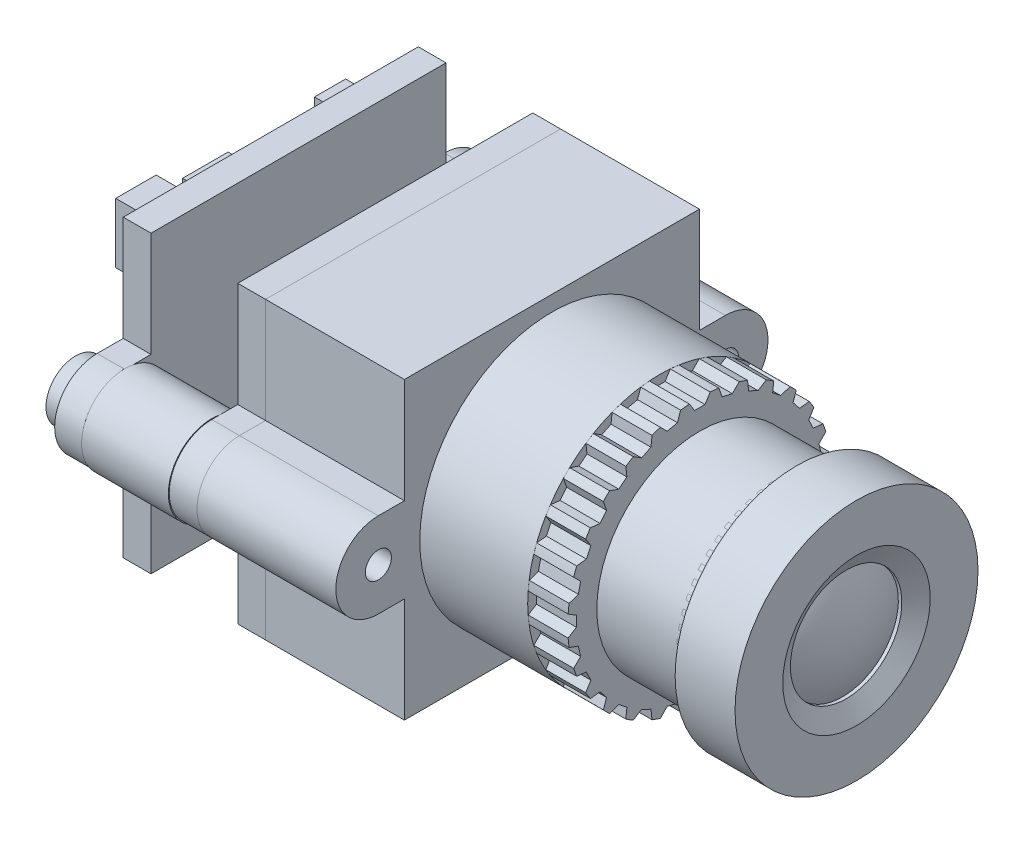
SolidWorks part; units mm, degrees
ref_plane "Front Plane" through (0, 0, 0) normal (0, 0, 1) x (1, 0, 0)
ref_plane "Top Plane" through (0, 0, 0) normal (0, 1, 0) x (1, 0, 0)
ref_plane "Right Plane" through (0, 0, 0) normal (1, 0, 0) x (0, 0, -1)
ref_axis "Axis1" through (-11.8965, 0, 0) along (1, 0, 0)
sketch "Sketch1" plane through (0, 0, 0) normal (1, 0, 0) x (0, 0, -1)
  circle A0 centre (0, 0) radius 7
  dimension "D1" = 14
extrude "Boss-Extrude1" add sketch "Sketch1" against normal blind 3.45
sketch "Sketch2" plane through (-3.45, 0, 0) normal (-1, 0, 0) x (0, 0, 1)
  circle A0 centre (0, 0) radius 5.935
  dimension "D1" = 11.87
extrude "Boss-Extrude2" add sketch "Sketch2" along normal blind 5.58
sketch "Sketch3" plane through (-9.03, 0, 0) normal (-1, 0, 0) x (0, 0, 1)
  circle A0 centre (0, 0) radius 7.61
  dimension "D1" = 15.22
extrude "Boss-Extrude3" add sketch "Sketch3" along normal blind 2.3
sketch "Sketch4" plane through (0, 0, 0) normal (0, 0, 1) x (1, 0, 0)
  line L0 (-3.45, 0) -> (0, 0) construction
  line L1 (-3.45, 5.935) -> (-3.45, -5.935) construction
  line L2 (0, -7) -> (0, 7) construction
  line L3 (0, 7) -> (-3.45, 7) construction
  line L4 (-0.6, 4.25) -> (0, 4.25)
  line L5 (-0.6, 4.25) -> (-0.6, -4.25)
  line L6 (-0.6, -4.25) -> (0, -4.25)
  line L7 (0, 4.25) -> (0, -4.25)
  line L8 (-0.6, 4.25) -> (0, -4.25) construction
  line L9 (-0.6, -4.25) -> (0, 4.25) construction
  line L10 (0, 4.25) -> (-0.6, 3.2108)
  line L11 (-0.8, 0) -> (-0.6, 3.2108) construction
  line L12 (-0.8, -3.2108) -> (-0.6, -3.2108)
  line L13 (-0.8, -3.2108) -> (-0.8, 3.2108)
  line L14 (-0.8, 3.2108) -> (-0.6, 3.2108)
  line L15 (-0.6, -3.2108) -> (-0.6, 3.2108)
  line L16 (-0.8, -3.2108) -> (-0.6, 3.2108) construction
  line L17 (-0.8, 3.2108) -> (-0.6, -3.2108) construction
  line L18 (-0.7, 1.6054) -> (0, 1.6054) construction
  line L19 (-0.8, 0) -> (0, 0)
  line L21 (0, 0) -> (0.6, 0)
  line L22 (0, 0) -> (0, 4.25)
  line L23 (0, 4.25) -> (0.6, 4.25)
  line L24 (0.6, 0) -> (0.6, 4.25)
  spline S0 degree 2 poles (0, 0) (0, 1.7034) (-0.8, 3.2108) knots 0 0 0 1 1 1
  point P6 (-0.3, 0)
  point P15 (-0.7, 0)
  dimension "D1" = 0.6
  dimension "D2" = 2.75
  dimension "D3" = 60
  dimension "D4" = 0.2
  dimension "D5" = 0.6
revolve "Cut-Revolve7" cut sketch "Sketch4" angle 360 about axis through (-11.8965, 0, 0) along (1, 0, 0) region at (0.3, 2.125, 0) region at (-0.2115, 2.72, 0) region at (-0.6658, 3.0768, 0)
sketch "Sketch5" plane through (-9.03, 0, 0) normal (1, 0, 0) x (0, 0, -1)
  line L0 (0, 7.61) -> (0, -7.61) construction
  line L1 (0.6, 7.5863) -> (0.3, 7.11)
  line L2 (0.3, 7.11) -> (-0.3, 7.11)
  line L3 (-0.6, 7.5863) -> (-0.3, 7.11)
  line L4 (2.2731, 7.2626) -> (1.8746, 6.865)
  line L5 (1.8746, 6.865) -> (1.2896, 6.9985)
  line L6 (1.1032, 7.5296) -> (1.2896, 6.9985)
  line L7 (3.8322, 6.5747) -> (3.3552, 6.2757)
  line L8 (3.3552, 6.2757) -> (2.8146, 6.5361)
  line L9 (2.751, 7.0954) -> (2.8146, 6.5361)
  line L10 (5.1991, 5.5571) -> (4.6676, 5.3718)
  line L11 (4.6676, 5.3718) -> (4.1985, 5.7459)
  line L12 (4.2609, 6.3053) -> (4.1985, 5.7459)
  line L13 (6.3053, 4.2609) -> (5.7459, 4.1985)
  line L14 (5.7459, 4.1985) -> (5.3718, 4.6676)
  line L15 (5.5571, 5.1991) -> (5.3718, 4.6676)
  line L16 (7.0954, 2.751) -> (6.5361, 2.8146)
  line L17 (6.5361, 2.8146) -> (6.2757, 3.3552)
  line L18 (6.5747, 3.8322) -> (6.2757, 3.3552)
  line L19 (7.5296, 1.1032) -> (6.9985, 1.2896)
  line L20 (6.9985, 1.2896) -> (6.865, 1.8746)
  line L21 (7.2626, 2.2731) -> (6.865, 1.8746)
  line L22 (7.5863, -0.6) -> (7.11, -0.3)
  line L23 (7.11, -0.3) -> (7.11, 0.3)
  line L24 (7.5863, 0.6) -> (7.11, 0.3)
  line L25 (7.2626, -2.2731) -> (6.865, -1.8746)
  line L26 (6.865, -1.8746) -> (6.9985, -1.2896)
  line L27 (7.5296, -1.1032) -> (6.9985, -1.2896)
  line L28 (6.5747, -3.8322) -> (6.2757, -3.3552)
  line L29 (6.2757, -3.3552) -> (6.5361, -2.8146)
  line L30 (7.0954, -2.751) -> (6.5361, -2.8146)
  line L31 (5.5571, -5.1991) -> (5.3718, -4.6676)
  line L32 (5.3718, -4.6676) -> (5.7459, -4.1985)
  line L33 (6.3053, -4.2609) -> (5.7459, -4.1985)
  line L34 (4.2609, -6.3053) -> (4.1985, -5.7459)
  line L35 (4.1985, -5.7459) -> (4.6676, -5.3718)
  line L36 (5.1991, -5.5571) -> (4.6676, -5.3718)
  line L37 (2.751, -7.0954) -> (2.8146, -6.5361)
  line L38 (2.8146, -6.5361) -> (3.3552, -6.2757)
  line L39 (3.8322, -6.5747) -> (3.3552, -6.2757)
  line L40 (1.1032, -7.5296) -> (1.2896, -6.9985)
  line L41 (1.2896, -6.9985) -> (1.8746, -6.865)
  line L42 (2.2731, -7.2626) -> (1.8746, -6.865)
  line L43 (-0.6, -7.5863) -> (-0.3, -7.11)
  line L44 (-0.3, -7.11) -> (0.3, -7.11)
  line L45 (0.6, -7.5863) -> (0.3, -7.11)
  line L46 (-2.2731, -7.2626) -> (-1.8746, -6.865)
  line L47 (-1.8746, -6.865) -> (-1.2896, -6.9985)
  line L48 (-1.1032, -7.5296) -> (-1.2896, -6.9985)
  line L49 (-3.8322, -6.5747) -> (-3.3552, -6.2757)
  line L50 (-3.3552, -6.2757) -> (-2.8146, -6.5361)
  line L51 (-2.751, -7.0954) -> (-2.8146, -6.5361)
  line L52 (-5.1991, -5.5571) -> (-4.6676, -5.3718)
  line L53 (-4.6676, -5.3718) -> (-4.1985, -5.7459)
  line L54 (-4.2609, -6.3053) -> (-4.1985, -5.7459)
  line L55 (-6.3053, -4.2609) -> (-5.7459, -4.1985)
  line L56 (-5.7459, -4.1985) -> (-5.3718, -4.6676)
  line L57 (-5.5571, -5.1991) -> (-5.3718, -4.6676)
  line L58 (-7.0954, -2.751) -> (-6.5361, -2.8146)
  line L59 (-6.5361, -2.8146) -> (-6.2757, -3.3552)
  line L60 (-6.5747, -3.8322) -> (-6.2757, -3.3552)
  line L61 (-7.5296, -1.1032) -> (-6.9985, -1.2896)
  line L62 (-6.9985, -1.2896) -> (-6.865, -1.8746)
  line L63 (-7.2626, -2.2731) -> (-6.865, -1.8746)
  line L64 (-7.5863, 0.6) -> (-7.11, 0.3)
  line L65 (-7.11, 0.3) -> (-7.11, -0.3)
  line L66 (-7.5863, -0.6) -> (-7.11, -0.3)
  line L67 (-7.2626, 2.2731) -> (-6.865, 1.8746)
  line L68 (-6.865, 1.8746) -> (-6.9985, 1.2896)
  line L69 (-7.5296, 1.1032) -> (-6.9985, 1.2896)
  line L70 (-6.5747, 3.8322) -> (-6.2757, 3.3552)
  line L71 (-6.2757, 3.3552) -> (-6.5361, 2.8146)
  line L72 (-7.0954, 2.751) -> (-6.5361, 2.8146)
  line L73 (-5.5571, 5.1991) -> (-5.3718, 4.6676)
  line L74 (-5.3718, 4.6676) -> (-5.7459, 4.1985)
  line L75 (-6.3053, 4.2609) -> (-5.7459, 4.1985)
  line L76 (-4.2609, 6.3053) -> (-4.1985, 5.7459)
  line L77 (-4.1985, 5.7459) -> (-4.6676, 5.3718)
  line L78 (-5.1991, 5.5571) -> (-4.6676, 5.3718)
  line L79 (-2.751, 7.0954) -> (-2.8146, 6.5361)
  line L80 (-2.8146, 6.5361) -> (-3.3552, 6.2757)
  line L81 (-3.8322, 6.5747) -> (-3.3552, 6.2757)
  line L82 (-1.1032, 7.5296) -> (-1.2896, 6.9985)
  line L83 (-1.2896, 6.9985) -> (-1.8746, 6.865)
  line L84 (-2.2731, 7.2626) -> (-1.8746, 6.865)
  circle A0 centre (0, 0) radius 7.61 construction
  circle A1 centre (0, 0) radius 7.61 construction
  circle A2 centre (0, 0) radius 7.61
  point P12 (0, 7.11)
  point P13 (0, 0)
  point P123 (0, 0)
  circle M6 centre (0, 0) radius 7.61
  dimension "D1" = 0.6
  dimension "D2" = 1.2
  dimension "D3" = 0.5
  dimension "D5" = 0.5063
  dimension "D4" = 28
extrude "Cut-Extrude1" cut sketch "Sketch5" against normal up to next (2.3 mm away) contours L9 L8 L7 M6 | L6 L5 L4 M6 | L0 L2 L1 M6 | L84 L83 L82 M6 | L0 A2 L3 L2 | L81 L80 L79 M6 | L78 L77 L76 M6 | L75 L74 L73 M6 | L72 L71 L70 M6 | L69 L68 L67 M6 | L66 L65 L64 M6 | L63 L62 L61 M6 | L60 L59 L58 M6 | L57 L56 L55 M6 | L51 L50 L49 M6 | L54 L53 L52 M6 | L48 L47 L46 M6 | L0 L44 L43 M6 | L44 L0 A2 L45 | L42 L41 L40 M6 | L39 L38 L37 M6 | L36 L35 L34 M6 | L33 L32 L31 M6 | L30 L29 L28 M6 | L27 L26 L25 M6 | L24 L23 L22 M6 | L21 L20 L19 M6 | L18 L17 L16 M6 | L15 L14 L13 M6 | L12 L11 L10 M6 region at (-9.03, 7.384, -0.233) region at (-9.03, 7.384, 0.233) region at (-9.03, -7.384, -0.233) region at (-9.03, -7.384, 0.233) region at (-9.03, 7.1989, -1.6431) region at (-9.03, 7.1989, 1.6431) region at (-9.03, 6.6527, -3.2038) region at (-9.03, 6.6527, 3.2038) region at (-9.03, -7.1989, 1.6431) region at (-9.03, -7.1989, -1.6431) region at (-9.03, 5.773, -4.6038) region at (-9.03, 5.773, 4.6038) region at (-9.03, -6.6527, 3.2038) region at (-9.03, -6.6527, -3.2038) region at (-9.03, 4.6038, -5.773) region at (-9.03, 4.6038, 5.773) region at (-9.03, -5.773, 4.6038) region at (-9.03, -5.773, -4.6038) region at (-9.03, 3.2038, -6.6527) region at (-9.03, 3.2038, 6.6527) region at (-9.03, -4.6038, 5.773) region at (-9.03, -4.6038, -5.773) region at (-9.03, 1.6431, -7.1989) region at (-9.03, 1.6431, 7.1989) region at (-9.03, -3.2038, 6.6527) region at (-9.03, -3.2038, -6.6527) region at (-9.03, 0, -7.384) region at (-9.03, 0, 7.384) region at (-9.03, -1.6431, 7.1989) region at (-9.03, -1.6431, -7.1989)
sketch "Sketch6" plane through (-11.33, 0, 0) normal (-1, 0, 0) x (0, 0, 1)
  line L0 (0, 7.615) -> (0, -7.615) construction
  line L2 (-8.5, -8.5) -> (8.5, -8.5)
  line L3 (-8.5, -8.5) -> (-8.5, 8.5)
  line L4 (-8.5, 8.5) -> (8.5, 8.5)
  line L5 (8.5, -8.5) -> (8.5, 8.5)
  line L6 (-8.5, -8.5) -> (8.5, 8.5) construction
  line L7 (-8.5, 8.5) -> (8.5, -8.5) construction
  line L8 (-1.25, -7.5117) -> (1.25, -7.5117)
  line L9 (-1.25, -7.5117) -> (-1.25, -8.5)
  line L10 (-1.25, -8.5) -> (1.25, -8.5)
  line L11 (1.25, -7.5117) -> (1.25, -8.5)
  line L12 (-1.25, -7.5117) -> (1.25, -8.5) construction
  line L13 (-1.25, -8.5) -> (1.25, -7.5117) construction
  circle A0 centre (0, 0) radius 7.615
  point P9 (0, -8.0059)
  point P14 (1.54, -7.4577)
  dimension "D1" = 15.23
  dimension "D2" = 17
  dimension "D3" = 2.5
extrude "Boss-Extrude4" add sketch "Sketch6" along normal offset from surface (6.22 mm away) 17.55 contours A0 L9 L2 L11 | A0 region at (-11.33, -8.0398, 0) up to face at (0, 0, 4.25)
sketch "Sketch7" plane through (-17.55, 0, 0) normal (-1, 0, 0) x (0, 0, 1)
  line L0 (1.25, -8.5) -> (-1.25, -8.5) construction
  line L1 (-8.5, -8.5) -> (8.5, -8.5)
  line L2 (-8.5, -8.5) -> (-8.5, 8.5)
  line L3 (-8.5, 8.5) -> (8.5, 8.5)
  line L4 (8.5, -8.5) -> (8.5, 8.5)
  line L5 (-8.5, -8.5) -> (8.5, 8.5) construction
  line L6 (-8.5, 8.5) -> (8.5, -8.5) construction
  line L7 (-8.5, 0) -> (8.5, 0) construction
  line L8 (0, 8.5) -> (0, -8.5) construction
  line L9 (-10, 2.45) -> (-8.5, 2.45)
  line L10 (-10, -2.45) -> (-8.5, -2.45)
  line L11 (10, 2.45) -> (8.5, 2.45)
  line L12 (10, -2.45) -> (8.5, -2.45)
  circle A0 centre (-10, 0) radius 2.45
  circle A1 centre (-10, 0) radius 0.75
  circle A2 centre (10, 0) radius 0.75
  circle A3 centre (10, 0) radius 2.45
  point P0 (0, 0)
  dimension "D1" = 4.9
  dimension "D3" = 1.5
  dimension "D2" = 20
extrude "Boss-Extrude5" add sketch "Sketch7" along normal blind 8 contours A0 L10 L2 | L2 A0 A1 | A0 L2 L9 | L12 A3 L4 | A3 L4 A2 | L4 A3 L11 | L1 L4 L3 L2 region at (-17.55, -2.2994, -8.8667) region at (-17.55, -2.2994, 8.8667) region at (-17.55, -2.2587, -9.2277) region at (-17.55, 0, 8.5629) region at (-17.55, 2.2994, -8.8667) region at (-17.55, 2.2994, 8.8667)
sketch "Sketch8" plane through (-25.55, 0, 0) normal (-1, 0, 0) x (0, 0, 1)
  line L10 (-10, -2.45) -> (-8.5, -2.45)
  line L11 (-8.5, -2.45) -> (-8.5, -8.5)
  line L12 (-8.5, -8.5) -> (8.5, -8.5)
  line L13 (8.5, -8.5) -> (8.5, -2.45)
  line L14 (8.5, -2.45) -> (10, -2.45)
  line L15 (10, 2.45) -> (8.5, 2.45)
  line L16 (8.5, 2.45) -> (8.5, 8.5)
  line L17 (8.5, 8.5) -> (-8.5, 8.5)
  line L18 (-8.5, 8.5) -> (-8.5, 2.45)
  line L19 (-8.5, 2.45) -> (-10, 2.45)
  line L20 (-10, -2.45) -> (-8.5, -2.45)
  line L21 (-8.5, -2.45) -> (-8.5, -8.5)
  line L22 (-8.5, -8.5) -> (8.5, -8.5)
  line L23 (8.5, -8.5) -> (8.5, -2.45)
  line L24 (8.5, -2.45) -> (10, -2.45)
  line L25 (10, 2.45) -> (8.5, 2.45)
  line L26 (8.5, 2.45) -> (8.5, 8.5)
  line L27 (8.5, 8.5) -> (-8.5, 8.5)
  line L28 (-8.5, 8.5) -> (-8.5, 2.45)
  line L29 (-8.5, 2.45) -> (-10, 2.45)
  circle A0 centre (10, 0) radius 0.75 construction
  circle A1 centre (-10, 0) radius 0.75 construction
  arc A2 (10, -2.45) -> (10, 2.45) centre (10, 0) ccw
  arc A3 (-10, 2.45) -> (-10, -2.45) centre (-10, 0) ccw
  arc A4 (10, -2.45) -> (10, 2.45) centre (10, 0) ccw
  arc A5 (-10, 2.45) -> (-10, -2.45) centre (-10, 0) ccw
  circle A6 centre (10, 0) radius 0.75
  circle A7 centre (-10, 0) radius 0.75
  dimension "D1" = 0
extrude "Boss-Extrude6" add sketch "Sketch8" along normal blind 1.6 separate body
sketch "Sketch9" plane through (-27.15, 0, 0) normal (-1, 0, 0) x (0, 0, 1)
  line L0 (0, 8.5) -> (0, -8.5) construction
  line L1 (8.5, 8.5) -> (-8.5, 8.5) construction
  line L2 (-8.5, -8.5) -> (8.5, -8.5) construction
  circle A0 centre (-10, 0) radius 2.5
  circle A1 centre (-10, 0) radius 1
  circle A2 centre (10, 0) radius 2.5
  circle A3 centre (10, 0) radius 1
  dimension "D1" = 5
  dimension "D2" = 2
extrude "Boss-Extrude7" add sketch "Sketch9" along normal blind 5 separate body
sketch "Sketch10" plane through (-32.15, 0, 0) normal (-1, 0, 0) x (0, 0, 1)
  line L10 (-10, -2.45) -> (-8.5, -2.45)
  line L11 (-8.5, -2.45) -> (-8.5, -8.5)
  line L12 (-8.5, -8.5) -> (8.5, -8.5)
  line L13 (8.5, -8.5) -> (8.5, -2.45)
  line L14 (8.5, -2.45) -> (10, -2.45)
  line L15 (10, 2.45) -> (8.5, 2.45)
  line L16 (8.5, 2.45) -> (8.5, 8.5)
  line L17 (8.5, 8.5) -> (-8.5, 8.5)
  line L18 (-8.5, 8.5) -> (-8.5, 2.45)
  line L19 (-8.5, 2.45) -> (-10, 2.45)
  line L20 (-10, -2.45) -> (-8.5, -2.45)
  line L21 (-8.5, -2.45) -> (-8.5, -8.5)
  line L22 (-8.5, -8.5) -> (8.5, -8.5)
  line L23 (8.5, -8.5) -> (8.5, -2.45)
  line L24 (8.5, -2.45) -> (10, -2.45)
  line L25 (10, 2.45) -> (8.5, 2.45)
  line L26 (8.5, 2.45) -> (8.5, 8.5)
  line L27 (8.5, 8.5) -> (-8.5, 8.5)
  line L28 (-8.5, 8.5) -> (-8.5, 2.45)
  line L29 (-8.5, 2.45) -> (-10, 2.45)
  circle A0 centre (-10, 0) radius 0.75 construction
  circle A1 centre (10, 0) radius 0.75 construction
  arc A2 (-10, 2.45) -> (-10, -2.45) centre (-10, 0) ccw
  arc A3 (10, -2.45) -> (10, 2.45) centre (10, 0) ccw
  arc A4 (-10, 2.45) -> (-10, -2.45) centre (-10, 0) ccw
  arc A5 (10, -2.45) -> (10, 2.45) centre (10, 0) ccw
  circle A6 centre (10, 0) radius 0.75
  circle A7 centre (-10, 0) radius 0.75
  dimension "D1" = 0
extrude "Boss-Extrude8" add sketch "Sketch10" along normal blind 1.6 separate body
sketch "Sketch11" plane through (-33.75, 0, 0) normal (-1, 0, 0) x (0, 0, 1)
  line L0 (0, 8.5) -> (0, -8.5) construction
  line L1 (8.5, 8.5) -> (-8.5, 8.5) construction
  line L2 (-8.5, -8.5) -> (8.5, -8.5) construction
  line L4 (-3.5, -4.7) -> (3.5, -4.7)
  line L5 (-3.5, -4.7) -> (-3.5, -7.9)
  line L6 (-3.5, -7.9) -> (3.5, -7.9)
  line L7 (3.5, -4.7) -> (3.5, -7.9)
  line L8 (-3.5, -4.7) -> (3.5, -7.9) construction
  line L9 (-3.5, -7.9) -> (3.5, -4.7) construction
  point P6 (0, -6.3)
  dimension "D1" = 7
  dimension "D2" = 3.2
  dimension "D3" = 0.6
extrude "Boss-Extrude9" add sketch "Sketch11" along normal blind 4.8 separate body
sketch "Sketch12" plane through (-38.55, 0, 0) normal (-1, 0, 0) x (0, 0, 1)
  line L0 (-3.5, -4.7) -> (3.5, -7.9) construction
  line L1 (3.5, -7.9) -> (3.5, -4.7) construction
  line L2 (-3.15, -7.55) -> (3.15, -7.55)
  line L3 (-3.15, -7.55) -> (-3.15, -5.05)
  line L4 (-3.15, -5.05) -> (3.15, -5.05)
  line L5 (3.15, -7.55) -> (3.15, -5.05)
  line L6 (-3.15, -7.55) -> (3.15, -5.05) construction
  line L7 (-3.15, -5.05) -> (3.15, -7.55) construction
  line L8 (3.15, -5.05) -> (3.5, -5.05) construction
  line L9 (3.15, -5.05) -> (3.15, -4.7) construction
  line L10 (3.5, -4.7) -> (-3.5, -4.7) construction
  point P4 (0, -6.3)
  dimension "D1" = 0.35
extrude "Cut-Extrude2" cut sketch "Sketch12" against normal offset from surface (4.4 mm away) 0.4 up to face at (-33.75, 0, 10.75)
sketch "Sketch13" plane through (-38.55, 0, 0) normal (-1, 0, 0) x (0, 0, 1)
  line L0 (0, -5.05) -> (0, -4.7) construction
  line L1 (3.15, -5.05) -> (-3.15, -5.05) construction
  line L2 (3.5, -4.7) -> (-3.5, -4.7) construction
  line L4 (-2.4, -5.05) -> (2.4, -5.05)
  line L5 (-2.4, -5.05) -> (-2.4, -4.7)
  line L6 (-2.4, -4.7) -> (2.4, -4.7)
  line L7 (2.4, -5.05) -> (2.4, -4.7)
  line L8 (-2.4, -5.05) -> (2.4, -4.7) construction
  line L9 (-2.4, -4.7) -> (2.4, -5.05) construction
  point P6 (0, -4.875)
  dimension "D1" = 4.8
extrude "Cut-Extrude3" cut sketch "Sketch13" against normal blind 1.5
sketch "Sketch14" plane through (-33.75, 0, 0) normal (-1, 0, 0) x (0, 0, 1)
  line L1 (6.733, 7.4544) -> (4.4023, 7.4544)
  line L2 (6.733, 7.4544) -> (6.733, 3.9954)
  line L3 (6.733, 3.9954) -> (4.4023, 3.9954)
  line L4 (4.4023, 7.4544) -> (4.4023, 3.9954)
  line L5 (3.6255, -8.0463) -> (5.9191, -8.0463)
  line L6 (3.6255, -8.0463) -> (3.6255, -4.1064)
  line L7 (3.6255, -4.1064) -> (5.9191, -4.1064)
  line L8 (5.9191, -8.0463) -> (5.9191, -4.1064)
  line L9 (-2.5526, -1.9607) -> (-0.9249, -1.9607)
  line L10 (-2.5526, -1.9607) -> (-2.5526, -3.8844)
  line L11 (-2.5526, -3.8844) -> (-0.9249, -3.8844)
  line L12 (-0.9249, -1.9607) -> (-0.9249, -3.8844)
  line L13 (-3.4035, 2.1827) -> (0.8694, 2.1827)
  line L14 (-3.4035, 2.1827) -> (-3.4035, 0.222)
  line L15 (-3.4035, 0.222) -> (0.8694, 0.222)
  line L16 (0.8694, 2.1827) -> (0.8694, 0.222)
  line L17 (-6.511, 6.7885) -> (-4.7168, 6.7885)
  line L18 (-6.511, 6.7885) -> (-6.511, 3.9954)
  line L19 (-6.511, 3.9954) -> (-4.7168, 3.9954)
  line L20 (-4.7168, 6.7885) -> (-4.7168, 3.9954)
  line L21 (0.259, 6.5295) -> (2.8856, 6.5295)
  line L22 (0.259, 6.5295) -> (0.259, 5.1977)
  line L23 (0.259, 5.1977) -> (2.8856, 5.1977)
  line L24 (2.8856, 6.5295) -> (2.8856, 5.1977)
extrude "Boss-Extrude10" add sketch "Sketch14" along normal blind 2.2
sketch "Sketch15" plane through (-33.75, 0, 0) normal (-1, 0, 0) x (0, 0, 1)
  circle A0 centre (-10, 0) radius 1.7
  circle A1 centre (10, 0) radius 1.7
  dimension "D1" = 3.4
extrude "Boss-Extrude11" add sketch "Sketch15" along normal blind 1.25
sketch "Sketch16" plane through (-3.45, 0, 0) normal (-1, 0, 0) x (0, 0, 1)
  circle A0 centre (0, 0) radius 5.935 construction
  circle A1 centre (0, 0) radius 5.935
extrude "Boss-Extrude12" add sketch "Sketch16" along normal blind 1 separate body
